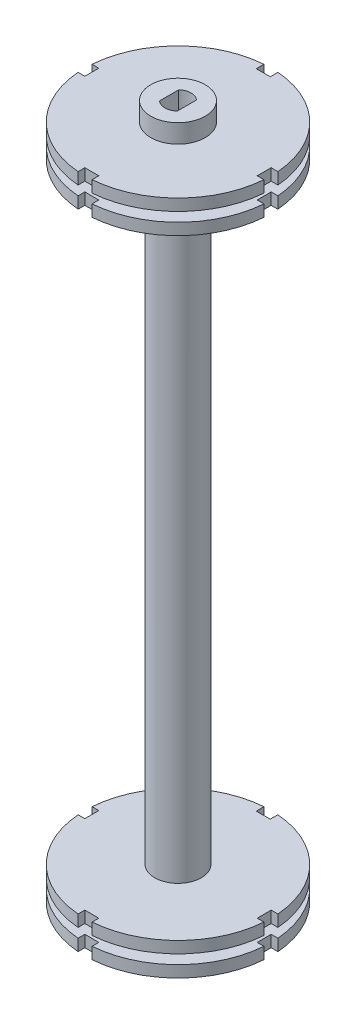
SolidWorks part; units mm, degrees
note: '?' marks a value the reader was unsure of.
ref_plane "Front Plane" through (0, 0, 0) normal (0, 0, 1) x (1, 0, 0)
ref_plane "Top Plane" through (0, 0, 0) normal (0, 1, 0) x (1, 0, 0)
ref_plane "Right Plane" through (0, 0, 0) normal (1, 0, 0) x (0, 0, -1)
sketch "Sketch1" plane through (0, 0, 0) normal (0, 1, 0) x (1, 0, 0)
  line L0 (1.9, 2.0567) -> (1.9, -2.0567)
  line L1 (-1.9, -2.0567) -> (-1.9, 2.0567)
  line L2 (-1.9, 2.0567) -> (-1.9, 5.5329)
  line L3 (1.9, 2.0567) -> (1.9, 5.5329)
  line L4 (-1.9, -2.0567) -> (-1.9, -5.5329)
  line L5 (1.9, -2.0567) -> (1.9, -5.5329)
  circle A0 centre (0, 0) radius 2.8
  circle A1 centre (0, 0) radius 5.85
  dimension "D1" = 5.6
  dimension "D4" = 11.7
  dimension "D2" = 1.9
  dimension "D3" = 1.9
extrude "Boss-Extrude1" add sketch "Sketch1" along normal blind 6.5 contours L2 A1 L4 A0 | L3 A1 L2 A0 | L5 A1 L3 A0 | L4 A1 L5 A0 | L1 A0 | L0 A0
sketch "Sketch2" plane through (0, 6.5, 0) normal (0, 1, 0) x (1, 0, 0)
  circle A0 centre (0, 0) radius 20
  dimension "D1" = 40
extrude "Boss-Extrude2" add sketch "Sketch2" against normal blind 2.5
sketch "Sketch3" plane through (0, 4, 0) normal (0, -1, 0) x (1, 0, 0)
  line L2 (-1.9, 2.0567) -> (-1.9, -2.0567)
  line L3 (1.9, -2.0567) -> (1.9, 2.0567)
  line L4 (-1.9, 2.0567) -> (-1.9, -2.0567)
  line L5 (1.9, -2.0567) -> (1.9, 2.0567)
  arc A2 (1.9, 2.0567) -> (-1.9, 2.0567) centre (0, 0) ccw
  arc A3 (-1.9, -2.0567) -> (1.9, -2.0567) centre (0, 0) ccw
  arc A4 (1.9, 2.0567) -> (-1.9, 2.0567) centre (0, 0) ccw
  arc A5 (-1.9, -2.0567) -> (1.9, -2.0567) centre (0, 0) ccw
  dimension "D1" = 0
extrude "Cut-Extrude1" cut sketch "Sketch3" against normal blind 8
sketch "Sketch4" plane through (0, 6.5, 0) normal (0, 1, 0) x (1, 0, 0)
  line L0 (0, 21.3) -> (0, 0) construction
  line L1 (-1.5, 21.3) -> (1.5, 21.3)
  line L2 (-1.5, 21.3) -> (-1.5, 18.3)
  line L3 (-1.5, 18.3) -> (1.5, 18.3)
  line L4 (1.5, 21.3) -> (1.5, 18.3)
  line L5 (0, 0) -> (32.685, 0) construction
  line L6 (0, 0) -> (0, -28.3806) construction
  line L7 (0, 0) -> (-25.3685, 0) construction
  line L9 (18.5, 1.5) -> (21.5, 1.5)
  line L10 (18.5, 1.5) -> (18.5, -1.5)
  line L11 (18.5, -1.5) -> (21.5, -1.5)
  line L12 (21.5, 1.5) -> (21.5, -1.5)
  line L13 (18.5, 1.5) -> (21.5, -1.5) construction
  line L14 (18.5, -1.5) -> (21.5, 1.5) construction
  line L15 (-1.5, -18.5) -> (1.5, -18.5)
  line L16 (-1.5, -18.5) -> (-1.5, -21.5)
  line L17 (-1.5, -21.5) -> (1.5, -21.5)
  line L18 (1.5, -18.5) -> (1.5, -21.5)
  line L19 (-1.5, -18.5) -> (1.5, -21.5) construction
  line L20 (-1.5, -21.5) -> (1.5, -18.5) construction
  line L21 (-21.5, 1.5) -> (-18.5, 1.5)
  line L22 (-21.5, 1.5) -> (-21.5, -1.5)
  line L23 (-21.5, -1.5) -> (-18.5, -1.5)
  line L24 (-18.5, 1.5) -> (-18.5, -1.5)
  line L25 (-21.5, 1.5) -> (-18.5, -1.5) construction
  line L26 (-21.5, -1.5) -> (-18.5, 1.5) construction
  circle A0 centre (0, 0) radius 20 construction
  point P12 (20, 0)
  point P17 (0, -20)
  point P22 (-20, 0)
  dimension "D1" = 3
  dimension "D2" = 3
  dimension "D3" = 18.3
  dimension "D4" = 3
  dimension "D5" = 3
  dimension "D6" = 3
  dimension "D7" = 3
  dimension "D8" = 3
  dimension "D9" = 3
ref_axis "Axis1" through (0, 6.5, 0) along (0, -1, 0)?
extrude "Cut-Extrude2" cut sketch "Sketch4" against normal blind 10
sketch "Sketch5" plane through (0, 6.5, 0) normal (0, 1, 0) x (1, 0, 0)
  circle A0 centre (0, 0) radius 5
  dimension "D1" = 10
extrude "Boss-Extrude3" add sketch "Sketch5" along normal blind 140
ref_plane "Plane1" through (0, 76.5, 0) normal (0, 1, 0) x (1, 0, 0)
mirror "Mirror1" about plane through (0, 76.5, 0) normal (0, 1, 0) of "Cut-Extrude2", "Boss-Extrude2"
mirror "Mirror2" about plane through (0, 76.5, 0) normal (0, 1, 0) of "Boss-Extrude1"
sketch "Sketch6" plane through (0, 6.5, 0) normal (0, -1, 0) x (1, 0, 0)
  line L2 (-1.9, 2.0567) -> (-1.9, -2.0567)
  line L3 (1.9, -2.0567) -> (1.9, 2.0567)
  line L4 (-1.9, 2.0567) -> (-1.9, -2.0567)
  line L5 (1.9, -2.0567) -> (1.9, 2.0567)
  arc A2 (1.9, 2.0567) -> (-1.9, 2.0567) centre (0, 0) ccw
  arc A3 (-1.9, -2.0567) -> (1.9, -2.0567) centre (0, 0) ccw
  arc A4 (1.9, 2.0567) -> (-1.9, 2.0567) centre (0, 0) ccw
  arc A5 (-1.9, -2.0567) -> (1.9, -2.0567) centre (0, 0) ccw
  dimension "D1" = 0
extrude "Cut-Extrude3" cut sketch "Sketch6" against normal blind 10
ref_plane "Plane2" through (0, 7.5, 0) normal (0, 1, 0) x (1, 0, 0)
mirror "Mirror3" about plane through (0, 7.5, 0) normal (0, 1, 0) of "Cut-Extrude2", "Boss-Extrude2"
ref_plane "Plane3" through (0, 145.5, 0) normal (0, -1, 0) x (-1, 0, 0)
mirror "Mirror5" about plane through (0, 145.5, 0) normal (0, -1, 0) of "Mirror1"
